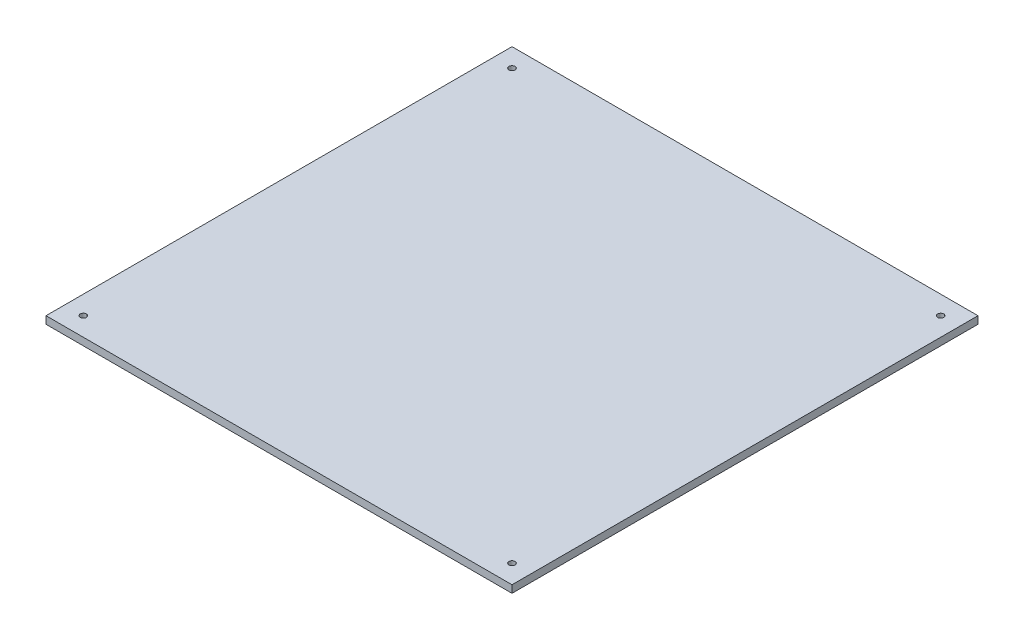
SolidWorks part; units mm, degrees
ref_plane "Front Plane" through (0, 0, 0) normal (0, 0, 1) x (1, 0, 0)
ref_plane "Top Plane" through (0, 0, 0) normal (0, 1, 0) x (1, 0, 0)
ref_plane "Right Plane" through (0, 0, 0) normal (1, 0, 0) x (0, 0, -1)
sketch "Sketch1" plane through (0, 0, 0) normal (0, 1, 0) x (1, 0, 0)
  line L0 (0, 125) -> (250, 125) construction
  line L1 (0, 0) -> (250, 0)
  line L2 (0, 0) -> (0, 250)
  line L3 (0, 250) -> (250, 250)
  line L4 (250, 0) -> (250, 250)
  line L5 (125, 250) -> (125, 0) construction
  circle A0 centre (10, 10) radius 1.65
  circle A1 centre (240, 10) radius 1.65
  circle A2 centre (240, 240) radius 1.65
  circle A3 centre (10, 240) radius 1.65
  dimension "D3" = 3.3
  dimension "D1" = 250
  dimension "D2" = 250
  dimension "D4" = 10
  dimension "D5" = 10
extrude "Boss-Extrude1" add sketch "Sketch1" along normal blind 4
equation "\"cf_tube_outer_diameter\" = 25mm"
equation "\"cf_tube_inner_diameter\" = 21mm"
equation "\"mid_plate_mid_to_top\" = 100mm"
equation "\"mid_plate_mid_to_bottom\" = 30mm"
equation "\"mid_plate_horizontal_spacing\" = 250mm"
equation "\"cf_plate_thickness\" = 4mm"
equation "\"mid_tube_length\" = 500mm"
equation "\"mid_plate_bottom_width\"= 180mm"
equation "\"D1@Sketch1\"=\"mid_plate_horizontal_spacing\""
equation "\"mid_support_plate_distance\" = 250mm"
equation "\"D2@Sketch1\"=\"mid_support_plate_distance\""
equation "\"D1@Boss-Extrude1\"=\"cf_plate_thickness\""
